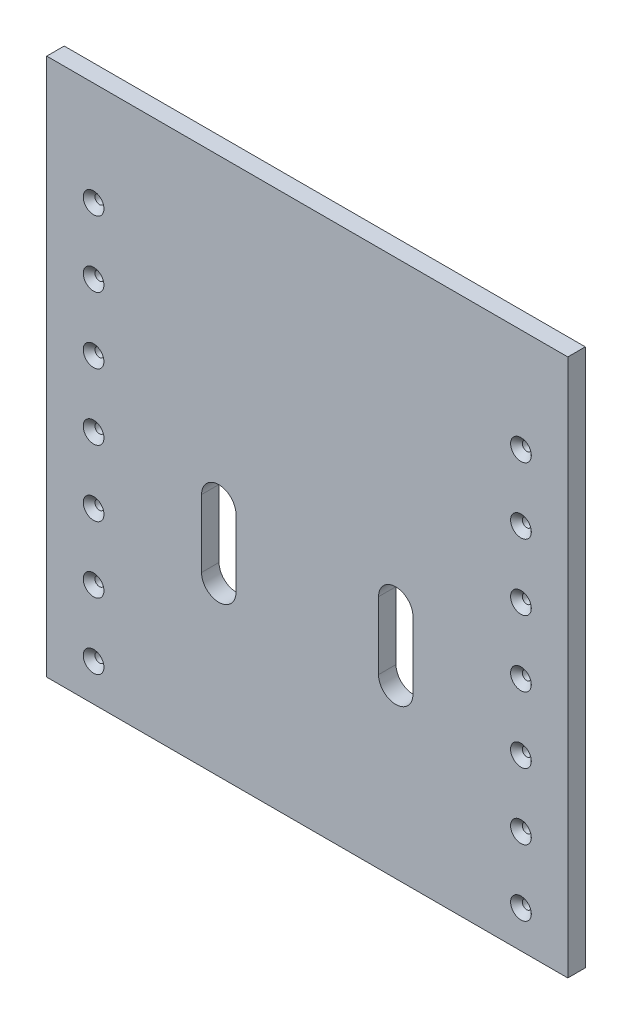
SolidWorks part; units mm, degrees
ref_plane "Front Plane" through (0, 0, 0) normal (0, 0, 1) x (1, 0, 0)
ref_plane "Top Plane" through (0, 0, 0) normal (0, 1, 0) x (1, 0, 0)
ref_plane "Right Plane" through (0, 0, 0) normal (1, 0, 0) x (0, 0, -1)
sketch "Sketch1" plane through (0, 0, 0) normal (0, 0, -1) x (1, 0, 0)
  line L1 (-203.2, 237) -> (-6.35, 237)
  line L2 (-203.2, 237) -> (-203.2, 33.8)
  line L3 (-203.2, 33.8) -> (-6.35, 33.8)
  line L4 (-6.35, 237) -> (-6.35, 33.8)
  dimension "D2" = 196.85
  dimension "D3" = 203.2
extrude "Boss-Extrude1" add sketch "Sketch1" along normal blind 6.604
sketch "Sketch2" plane through (0, 0, -6.604) normal (0, 0, -1) x (1, 0, 0)
  line L0 (-138.2, 180) -> (-138.2, 141.5) construction
  line L1 (-6.35, 237) -> (-203.2, 237) construction
  line L2 (-138.2, 180) -> (-138.2, 237) construction
  line L3 (-138.2, 173.5) -> (-138.2, 148) construction
  line L6 (-131.7, 173.5) -> (-131.7, 148)
  line L7 (-144.7, 173.5) -> (-144.7, 148)
  line L8 (-138.2, 160.75) -> (-203.2, 160.75) construction
  line L9 (-203.2, 237) -> (-203.2, 33.8) construction
  line L10 (-71.35, 180) -> (-71.35, 141.5) construction
  line L11 (-71.35, 180) -> (-71.35, 237) construction
  line L12 (-71.35, 173.5) -> (-71.35, 148) construction
  line L16 (-64.85, 173.5) -> (-64.85, 148)
  line L17 (-77.85, 173.5) -> (-77.85, 148)
  line L18 (-71.35, 160.75) -> (-6.35, 160.75) construction
  line L19 (-6.35, 33.8) -> (-6.35, 237) construction
  arc A2 (-131.7, 173.5) -> (-144.7, 173.5) centre (-138.2, 173.5) ccw
  arc A3 (-144.7, 148) -> (-131.7, 148) centre (-138.2, 148) ccw
  arc A6 (-64.85, 173.5) -> (-77.85, 173.5) centre (-71.35, 173.5) ccw
  arc A7 (-77.85, 148) -> (-64.85, 148) centre (-71.35, 148) ccw
  point P5 (-138.2, 160.75)
  point P18 (-71.35, 160.75)
  dimension "D4" = 6.5
  dimension "D6" = 57
  dimension "D5" = 6.5
  dimension "D1" = 65
  dimension "D2" = 57
  dimension "D3" = 38.5
  dimension "D7" = 65
  dimension "D8" = 38.5
extrude "Cut-Extrude7" cut sketch "Sketch2" against normal through all
ref_plane "Plane1" through (-104.775, 0, 0) normal (1, 0, 0) x (0, 0, -1)
sketch "Sketch4" plane through (0, 0, 0) normal (0, 0, 1) x (1, 0, 0)
  line L0 (-203.2, -33.8) -> (-6.35, -33.8) construction
  line L1 (-3.2035, -33.8) -> (-200.0535, -33.8)
  line L2 (-3.2035, -33.8) -> (-3.2035, -34.4096)
  line L3 (-3.2035, -34.4096) -> (-200.0535, -34.4096)
  line L4 (-200.0535, -33.8) -> (-200.0535, -34.4096)
  line L5 (-3.2035, -237.9465) -> (-3.2035, 1.0535) construction
  line L6 (-200.0535, 1.0535) -> (-200.0535, -237.9465) construction
  dimension "D1" = 0.6096
extrude "Boss-Extrude2" add sketch "Sketch4" along normal blind 12
sketch "Sketch8" plane through (0, 0, -6.604) normal (0, 0, -1) x (-1, 0, 0)
  circle A0 centre (185.47, -222) radius 3.75
  circle A1 centre (185.47, -197) radius 3.75
  circle A2 centre (185.47, -172) radius 3.75
  circle A3 centre (185.47, -147) radius 3.75
  circle A4 centre (185.47, -122) radius 3.75
  circle A5 centre (185.47, -97) radius 3.75
  dimension "D1" = 7.5
sketch "Sketch13" plane through (0, 0, 12) normal (0, 0, 1) x (1, 0, 0)
  line L1 (-3.2035, -34.4096) -> (-200.0535, -34.4096)
  line L2 (-3.2035, -34.4096) -> (-3.2035, -33.8)
  line L3 (-3.2035, -33.8) -> (-200.0535, -33.8)
  line L4 (-200.0535, -34.4096) -> (-200.0535, -33.8)
sketch "Sketch14" plane through (0, 0, 0) normal (0, 0, 1) x (1, 0, 0)
  line L0 (-6.35, -34.4096) -> (-6.35, -237) construction
  line L1 (-6.35, -59.904) -> (-203.2, -59.904)
  line L2 (-6.35, -59.904) -> (-6.35, -47.966)
  line L3 (-6.35, -47.966) -> (-203.2, -47.966)
  line L4 (-203.2, -59.904) -> (-203.2, -47.966)
  line L5 (-203.2, -237) -> (-203.2, -33.8) construction
  dimension "D1" = 11.938
extrude "Boss-Extrude3" add sketch "Sketch14" against normal up to surface (6.604 mm away) up to face at (-138.2, -160.75, -6.604)
extrude "Cut-Extrude9" cut sketch "Sketch13" against normal up to surface (12 mm away) up to face at (-71.35, -160.75, 0)
hole_wizard "CSK for M3 Flat Head Machine Screw3" positions "Sketch15" profile "Sketch16" countersink size "M3" standard "ANSI Metric" end condition through all
sketch "Sketch15" plane through (0, 0, 0) normal (0, 0, 1) x (1, 0, 0)
  point P18 (-185.4985, -72.9465)
  point P21 (-185.4985, -222.9465)
  point P24 (-185.4985, -197.9465)
  point P27 (-185.4985, -172.9465)
  point P30 (-185.4985, -147.9465)
  point P33 (-185.4985, -122.9465)
  point P36 (-185.4985, -97.9465)
  point P39 (-185.4985, -72.9465)
sketch "Sketch16" plane through (-185.4985, -72.9465, 0) normal (1, 0, 0) x (0, -1, 0)
  line L0 (0, 0) -> (0, 6.604)
  line L1 (0, 6.604) -> (1.7, 6.604)
  line L2 (1.7, 6.604) -> (1.7, 2.212)
  line L3 (1.7, 2.212) -> (3.912, 0)
  line L5 (3.912, 0) -> (0, 0)
  line L6 (-1.7, 2.212) -> (-3.912, 0) construction
  line L11 (0, -6.35) -> (0, 107.95) construction
  dimension "Thru Hole Dia." = 3.4
  dimension "Thru Hole Depth" = 6.604
  dimension "Near C'Sink Dia." = 7.824
  dimension "Near C'Sink Angle" = 90
ref_plane "Plane2" through (-104.775, 0, 0) normal (-1, 0, 0) x (0, 0, 1)
mirror "Mirror1" about plane through (-104.775, 0, 0) normal (-1, 0, 0) of "CSK for M3 Flat Head Machine Screw3"
